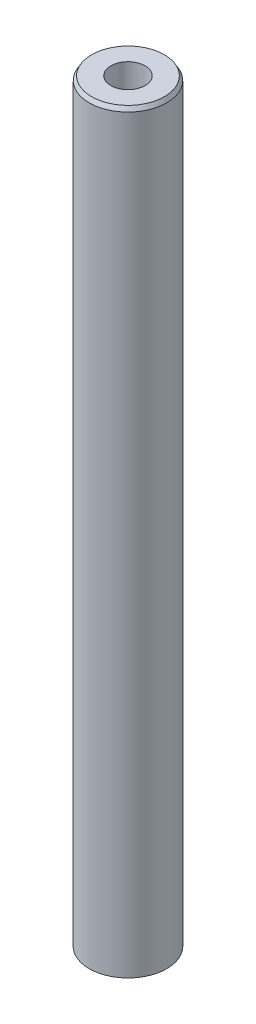
SolidWorks part; units mm, degrees
ref_plane "Front Plane" through (0, 0, 0) normal (0, 0, 1) x (1, 0, 0)
ref_plane "Top Plane" through (0, 0, 0) normal (0, 1, 0) x (1, 0, 0)
ref_plane "Right Plane" through (0, 0, 0) normal (1, 0, 0) x (0, 0, -1)
sketch "Sketch1" plane through (0, 0, 0) normal (0, 1, 0) x (1, 0, 0)
  circle A0 centre (0, 0) radius 30
  dimension "SHAFT_OD" = 60
extrude "Boss-Extrude1" add sketch "Sketch1" along normal blind 585.7301
sketch "Sketch2" plane through (0, 0, 0) normal (0, 1, 0) x (1, 0, 0)
  circle A0 centre (0, 0) radius 13.2899
  dimension "BORE_D" = 26.5797
extrude "Cut-Extrude1" cut sketch "Sketch2" along normal through all
chamfer "Chamfer1" distance 3.2025 angle 30 2 edges at (0, 585.7301, 30) (0, 0, 30) first distance on face at (0, 585.7301, 30) first distance on face at (0, 0, 13.2899)
